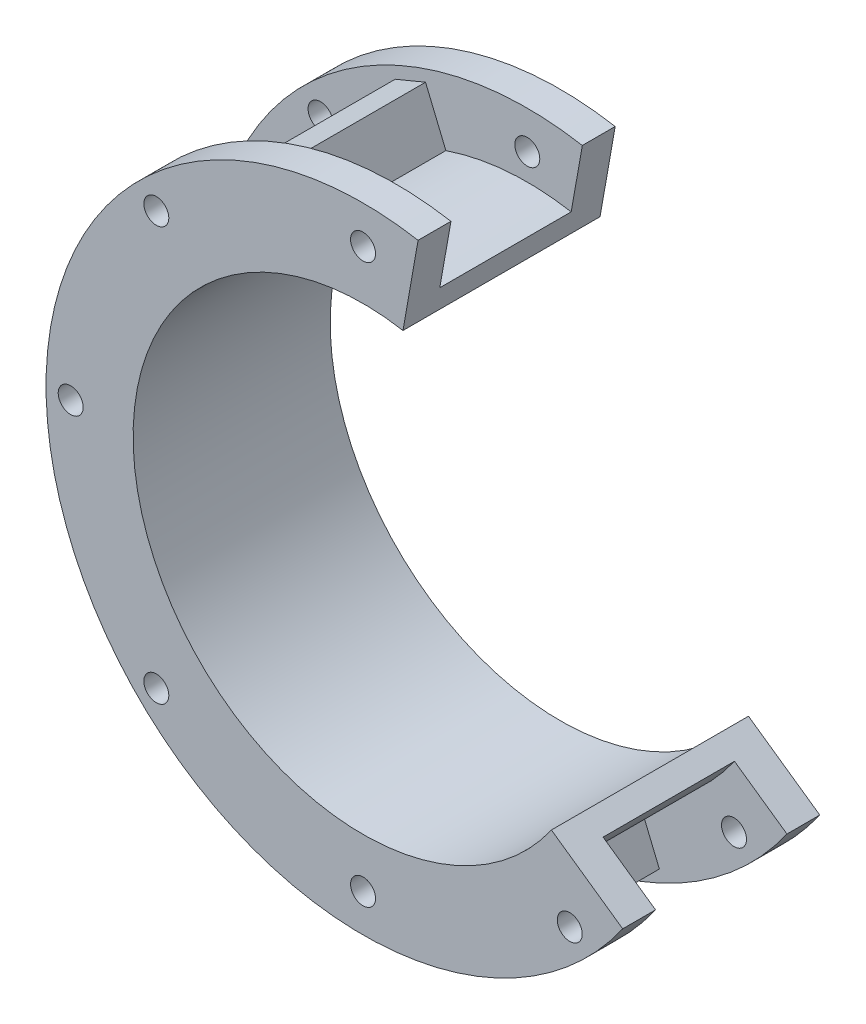
SolidWorks part; units mm, degrees
note: The reader was unsure of these and kept them because the rebuilt part matched: shared geometry of "草图2<3>".
ref_plane "前视基准面" through (0, 0, 0) normal (0, 0, 1) x (1, 0, 0)
ref_plane "上视基准面" through (0, 0, 0) normal (0, 1, 0) x (1, 0, 0)
ref_plane "右视基准面" through (0, 0, 0) normal (1, 0, 0) x (0, 0, -1)
other "Configuration Table"
sketch "草图1" plane through (0, 0, 0) normal (0, 0, 1) x (1, 0, 0)
  circle A0 centre (0, 0) radius 48.25
  dimension "D1" = 96.5
extrude "凸台-拉伸1" add sketch "草图1" along normal blind 30
sketch "草图2" plane through (0, 0, 30) normal (0, 0, 1) x (1, 0, 0)
  line L0 (0, 0) -> (39.5241, -27.6751)
  line L1 (0, 0) -> (0, -48.25) construction
  line L2 (0, 0) -> (34.1179, -34.1179) construction
  line L3 (0, 0) -> (8.3785, 47.517)
  circle A0 centre (0, 0) radius 35
  circle A1 centre (0, 0) radius 48.25 construction
  circle A2 centre (0, 0) radius 48.25
  dimension "D1" = 70
  dimension "D2" = 10
  dimension "D3" = 45
  dimension "D4" = 55
extrude "切除-拉伸1" cut sketch "草图2" against normal through all both and the other way through all
extrude "切除-拉伸2" cut sketch "草图2<3>" against normal through all both and the other way through all
sketch "草图2<3>" plane through (0, 0, 30) normal (0, 0, 1) x (1, 0, 0) same geometry as "草图2"
sketch "草图3" plane through (0, 0, 0) normal (0, 0, 1) x (1, 0, 0)
  line L0 (0, 0) -> (0, 42.5) construction
  line L1 (0, 0) -> (11.3856, 0) construction
  circle A0 centre (0, 0) radius 44.5 construction
  circle A1 centre (0, 44.5) radius 1.9 construction
  circle A2 centre (31.4663, 31.4663) radius 1.9
  circle A3 centre (44.5, 0) radius 1.9
  circle A4 centre (31.4663, -31.4663) radius 1.9
  circle A5 centre (0, -44.5) radius 1.9 construction
  circle A6 centre (-31.4663, -31.4663) radius 1.9
  circle A7 centre (0, 42.5) radius 1.9
  circle A8 centre (0, -42.5) radius 1.9
  circle A9 centre (-44.5, 0) radius 1.9
  circle A10 centre (-31.4663, 31.4663) radius 1.9
  point P17 (0, 0)
  dimension "D1" = 89
  dimension "D2" = 3.8
  dimension "D4" = 3.8
  dimension "D5" = 42.5
  dimension "D3" = 8
extrude "切除-拉伸3" cut sketch "草图3" against normal through all both and the other way through all
sketch "草图4" plane through (0, 0, 0) normal (0, 0, 1) x (1, 0, 0)
  circle A0 centre (0, 0) radius 38.5
  dimension "D1" = 77
extrude "切除-拉伸4" cut sketch "草图4" along normal blind 20 from offset 5 flip side to cut
ref_plane "基准面1" through (0, 0, 0) normal (0.9239, 0.3827, 0) x (0, 0, 1)
sketch "草图8" plane through (0, 0, 0) normal (0.9239, 0.3827, 0) x (0, 0, 1)
  line L0 (5, 46.5) -> (25, 46.5)
  line L1 (5, -48.25) -> (5, 48.25) construction
  line L2 (25, 48.25) -> (25, -48.25) construction
  line L3 (25, 38.5) -> (5, 38.5) construction
  dimension "D1" = 8
rib "筋4" sketch "草图8" sketch "草图8" thickness 5 extrusion direction parallel to sketch draft on no parameters "D1"=5
pattern_circular "阵列(圆周)1" count 5 every 45 about axis through (0, 0, 0) along (0, 0, 1) of "筋4"
